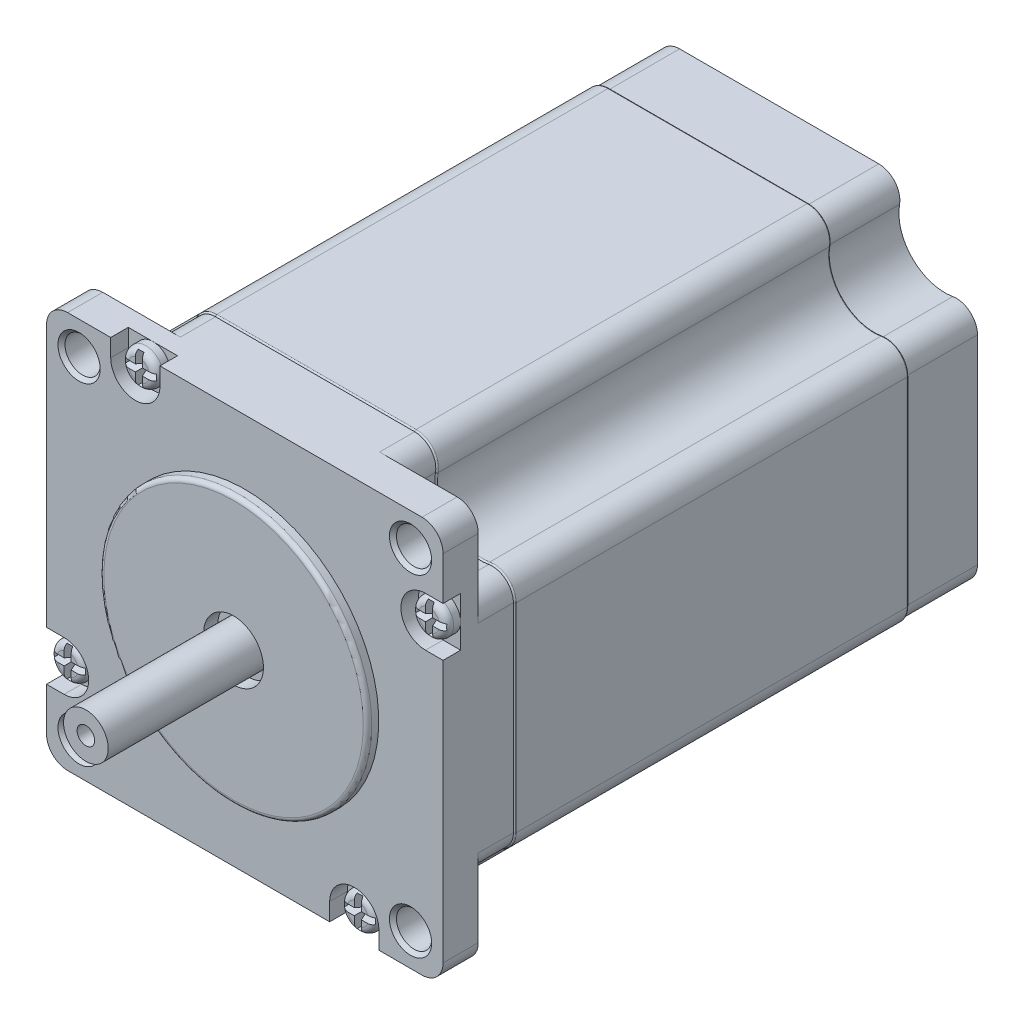
SolidWorks part; units mm, degrees
ref_plane "Front Plane" through (0, 0, 0) normal (0, 0, 1) x (1, 0, 0)
ref_plane "Top Plane" through (0, 0, 0) normal (0, 1, 0) x (1, 0, 0)
ref_plane "Right Plane" through (0, 0, 0) normal (1, 0, 0) x (0, 0, -1)
sketch "Sketch1" plane through (0, 0, 0) normal (0, 0, 1) x (1, 0, 0)
  line L1 (0, 0) -> (56.4, 0)
  line L2 (0, 0) -> (0, 56.4)
  line L3 (0, 56.4) -> (56.4, 56.4)
  line L4 (56.4, 0) -> (56.4, 56.4)
  dimension "D1" = 56.4
extrude "Boss-Extrude1" add sketch "Sketch1" along normal blind 76
sketch "Sketch2" plane through (0, 0, 76) normal (0, 0, 1) x (1, 0, 0)
  line L0 (28.2, 56.4) -> (28.2, 0) construction
  line L1 (56.4, 56.4) -> (0, 56.4) construction
  line L2 (0, 0) -> (56.4, 0) construction
  line L3 (28.2, 0) -> (0, 28.2) construction
  line L4 (0, 56.4) -> (0, 0) construction
  line L5 (0, 28.2) -> (56.4, 28.2) construction
  line L6 (56.4, 0) -> (56.4, 56.4) construction
  circle A0 centre (4.63, 51.77) radius 2.5
  circle A1 centre (51.77, 51.77) radius 2.5
  circle A2 centre (51.77, 4.63) radius 2.5
  circle A3 centre (4.63, 4.63) radius 2.5
  dimension "D3" = 5
  dimension "D1" = 23.57
  dimension "D2" = 47.14
extrude "Cut-Extrude1" cut sketch "Sketch2" against normal up to next
sketch "Sketch3" plane through (0, 0, 0) normal (0, 0, -1) x (-1, 0, 0)
  circle A0 centre (-51.77, 51.77) radius 6.5478
  circle A1 centre (-4.63, 51.77) radius 6.5478
  circle A2 centre (-4.63, 4.63) radius 6.5478
  circle A3 centre (-51.77, 4.63) radius 6.5478
extrude "Cut-Extrude2" cut sketch "Sketch3" against normal offset from surface (71 mm away) 5 up to face at (2.13, 4.63, 76)
fillet "Fillet1" radius 3 12 edges at (0, 9.26, 35.5) (9.26, 0, 35.5) (9.26, 56.4, 35.5) (0, 47.14, 35.5) (47.14, 0, 35.5) (56.4, 9.26, 35.5) (56.4, 47.14, 35.5) (47.14, 56.4, 35.5) (56.4, 56.4, 73.5) (56.4, 0, 73.5) (0, 56.4, 73.5) (0, 0, 73.5)
sketch "Sketch4" plane through (0, 0, 76) normal (0, 0, 1) x (1, 0, 0)
  line L0 (0, 28.2) -> (56.4, 28.2) construction
  line L1 (0, 53.4) -> (0, 3) construction
  line L2 (56.4, 3) -> (56.4, 53.4) construction
  circle A0 centre (28.2, 28.2) radius 19.05
  dimension "D1" = 38.1
extrude "Boss-Extrude2" add sketch "Sketch4" along normal blind 1.6
fillet "Fillet2" radius 0.6 1 edges at (47.25, 28.2, 77.6)
sketch "Sketch5" plane through (0, 0, 77.6) normal (0, 0, 1) x (1, 0, 0)
  line L0 (28.2, 46.65) -> (28.2, 28.2) construction
  circle A0 centre (28.2, 28.2) radius 18.45 construction
  circle A1 centre (28.2, 28.2) radius 3.175
  circle A2 centre (28.2, 28.2) radius 1.25
  dimension "D1" = 6.35
  dimension "D2" = 2.5
extrude "Boss-Extrude3" add sketch "Sketch5" along normal blind 21
sketch "Sketch6" plane through (0, 0, 77.6) normal (0, 0, 1) x (1, 0, 0)
  circle A0 centre (28.2, 28.2) radius 4.25
  circle A1 centre (28.2, 28.2) radius 3.175 construction
  circle A2 centre (28.2, 28.2) radius 3.175
  dimension "D1" = 8.5
extrude "Cut-Extrude3" cut sketch "Sketch6" against normal blind 2
ref_plane "Plane1" through (0, 0, 10) normal (0, 0, -1) x (-1, 0, 0)
sketch "Sketch7" plane through (0, 0, 10) normal (0, 0, -1) x (-1, 0, 0)
  line L0 (-56.4, 14.0376) -> (-56.4, 42.3624) construction
  line L1 (-42.3624, 56.4) -> (-14.0376, 56.4) construction
  line L2 (-56.4, 14.0376) -> (-56.4, 42.3624)
  line L3 (-42.3624, 56.4) -> (-14.0376, 56.4)
  line L4 (-56.2, 14.0376) -> (-56.2, 42.3624)
  line L5 (-42.3624, 56.2) -> (-14.0376, 56.2)
  line L6 (-42.3624, -0.2) -> (-14.0376, -0.2)
  line L7 (0.2, 14.0376) -> (0.2, 42.3624)
  line L8 (-42.3624, 0) -> (-14.0376, 0)
  line L9 (0, 14.0376) -> (0, 42.3624)
  line L10 (-14.0376, 56.4) -> (-42.3624, 56.4)
  line L11 (-56.4, 42.3624) -> (-56.4, 14.0376)
  line L12 (-42.3624, 0) -> (-14.0376, 0)
  line L13 (0, 14.0376) -> (0, 42.3624)
  line L14 (-14.0376, 56.4) -> (-42.3624, 56.4)
  line L15 (-56.4, 42.3624) -> (-56.4, 14.0376)
  line L16 (-14.0376, 56.6) -> (-42.3624, 56.6)
  line L17 (-56.6, 42.3624) -> (-56.6, 14.0376)
  arc A0 (-52.8878, 45.3183) -> (-56.4, 42.3624) centre (-53.4, 42.3624) ccw construction
  arc A1 (-52.8878, 45.3183) -> (-45.3183, 52.8878) centre (-51.77, 51.77) ccw construction
  arc A2 (-42.3624, 56.4) -> (-45.3183, 52.8878) centre (-42.3624, 53.4) ccw construction
  arc A3 (-52.8878, 45.3183) -> (-56.4, 42.3624) centre (-53.4, 42.3624) ccw
  arc A4 (-52.8878, 45.3183) -> (-45.3183, 52.8878) centre (-51.77, 51.77) ccw
  arc A5 (-42.3624, 56.4) -> (-45.3183, 52.8878) centre (-42.3624, 53.4) ccw
  arc A6 (-56.6, 14.0376) -> (-52.8537, 10.8846) centre (-53.4, 14.0376) ccw
  arc A7 (-45.5154, 3.5463) -> (-52.8537, 10.8846) centre (-51.77, 4.63) ccw
  arc A8 (-45.5154, 3.5463) -> (-42.3624, -0.2) centre (-42.3624, 3) ccw
  arc A9 (-14.0376, -0.2) -> (-10.8846, 3.5463) centre (-14.0376, 3) ccw
  arc A10 (-3.5463, 10.8846) -> (-10.8846, 3.5463) centre (-4.63, 4.63) ccw
  arc A11 (-3.5463, 10.8846) -> (0.2, 14.0376) centre (-3, 14.0376) ccw
  arc A12 (0.2, 42.3624) -> (-3.5463, 45.5154) centre (-3, 42.3624) ccw
  arc A13 (-10.8846, 52.8537) -> (-3.5463, 45.5154) centre (-4.63, 51.77) ccw
  arc A14 (-10.8846, 52.8537) -> (-14.0376, 56.6) centre (-14.0376, 53.4) ccw
  arc A15 (-52.8537, 45.5154) -> (-56.6, 42.3624) centre (-53.4, 42.3624) ccw
  arc A16 (-42.3624, 56.6) -> (-45.5154, 52.8537) centre (-42.3624, 53.4) ccw
  arc A17 (-42.3624, 56.6) -> (-45.5154, 52.8537) centre (-42.3624, 53.4) ccw
  arc A18 (-14.0376, 0) -> (-11.0817, 3.5122) centre (-14.0376, 3) ccw
  arc A19 (-3.5122, 11.0817) -> (-11.0817, 3.5122) centre (-4.63, 4.63) ccw
  arc A20 (-3.5122, 11.0817) -> (0, 14.0376) centre (-3, 14.0376) ccw
  arc A21 (0, 42.3624) -> (-3.5122, 45.3183) centre (-3, 42.3624) ccw
  arc A22 (-11.0817, 52.8878) -> (-3.5122, 45.3183) centre (-4.63, 51.77) ccw
  arc A23 (-11.0817, 52.8878) -> (-14.0376, 56.4) centre (-14.0376, 53.4) ccw
  arc A24 (-42.3624, 56.4) -> (-45.3183, 52.8878) centre (-42.3624, 53.4) ccw
  arc A25 (-52.8878, 45.3183) -> (-45.3183, 52.8878) centre (-51.77, 51.77) ccw
  arc A26 (-52.8878, 45.3183) -> (-56.4, 42.3624) centre (-53.4, 42.3624) ccw
  arc A27 (-56.4, 14.0376) -> (-52.8878, 11.0817) centre (-53.4, 14.0376) ccw
  arc A28 (-45.3183, 3.5122) -> (-52.8878, 11.0817) centre (-51.77, 4.63) ccw
  arc A29 (-45.3183, 3.5122) -> (-42.3624, 0) centre (-42.3624, 3) ccw
  arc A30 (-14.0376, 0) -> (-11.0817, 3.5122) centre (-14.0376, 3) ccw
  arc A31 (-3.5122, 11.0817) -> (-11.0817, 3.5122) centre (-4.63, 4.63) ccw
  arc A32 (-3.5122, 11.0817) -> (0, 14.0376) centre (-3, 14.0376) ccw
  arc A33 (0, 42.3624) -> (-3.5122, 45.3183) centre (-3, 42.3624) ccw
  arc A34 (-11.0817, 52.8878) -> (-3.5122, 45.3183) centre (-4.63, 51.77) ccw
  arc A35 (-11.0817, 52.8878) -> (-14.0376, 56.4) centre (-14.0376, 53.4) ccw
  arc A36 (-42.3624, 56.4) -> (-45.3183, 52.8878) centre (-42.3624, 53.4) ccw
  arc A37 (-52.8878, 45.3183) -> (-45.3183, 52.8878) centre (-51.77, 51.77) ccw
  arc A38 (-52.8878, 45.3183) -> (-56.4, 42.3624) centre (-53.4, 42.3624) ccw
  arc A39 (-56.4, 14.0376) -> (-52.8878, 11.0817) centre (-53.4, 14.0376) ccw
  arc A40 (-45.3183, 3.5122) -> (-52.8878, 11.0817) centre (-51.77, 4.63) ccw
  arc A41 (-45.3183, 3.5122) -> (-42.3624, 0) centre (-42.3624, 3) ccw
  arc A42 (-52.8537, 45.5154) -> (-45.5154, 52.8537) centre (-51.77, 51.77) ccw
  arc A43 (-52.8537, 45.5154) -> (-56.6, 42.3624) centre (-53.4, 42.3624) ccw
  dimension "D1" = 0
  dimension "D2" = 0.2
  dimension "D3" = 0.2
extrude "Boss-Extrude4" add sketch "Sketch7" against normal blind 56 contours A42 A15 L17 A6 A7 A8 L6 A9 A10 A11 L7 A12 A13 A14 L16 A16 A41 A40 A39 L2 A3 A4 A5 L3 A35 A34 A33 L13 A32 A31 A30 L12 region at (44.7492, 0.9912, 10)
fillet "Fillet4" radius 0.2 32 edges at (55.4606, 44.8106, 66) (56.6, 28.2, 66) (55.4606, 11.5894, 66) (47.2814, 9.1186, 66) (44.8106, 0.9394, 66) (28.2, -0.2, 66) (11.5894, 0.9394, 66) (9.1186, 9.1186, 66) (0.9394, 11.5894, 66) (-0.2, 28.2, 66) (0.9394, 44.8106, 66) (9.1186, 47.2814, 66) (11.5894, 55.4606, 66) (28.2, 56.6, 66) (44.8106, 55.4606, 66) (44.8106, 55.4606, 10) (28.2, 56.6, 10) (11.5894, 55.4606, 10) (9.1186, 47.2814, 10) (0.9394, 44.8106, 10) (-0.2, 28.2, 10) (0.9394, 11.5894, 10) (9.1186, 9.1186, 10) (11.5894, 0.9394, 10) (28.2, -0.2, 10) (44.8106, 0.9394, 10) (47.2814, 9.1186, 10) (55.4606, 11.5894, 10) (56.6, 28.2, 10) (47.2814, 47.2814, 66) (47.2814, 47.2814, 10) (55.4606, 44.8106, 10)
chamfer "Chamfer1" distance 0.5 angle 45 4 edges at (2.13, 4.63, 76) (54.27, 4.63, 76) (49.27, 51.77, 76) (7.13, 51.77, 76)
sketch "Sketch8" plane through (0, 0, 76) normal (0, 0, 1) x (1, 0, 0)
  line L0 (53.4, 56.4) -> (3, 56.4) construction
  line L1 (9.13, 53.9) -> (9.13, 56.4)
  line L2 (16.13, 53.9) -> (16.13, 56.4)
  line L3 (42.3624, 56.4) -> (14.0376, 56.4) construction
  line L4 (16.13, 56.4) -> (9.13, 56.4)
  arc A0 (9.13, 53.9) -> (16.13, 53.9) centre (12.63, 53.9) ccw
  circle A1 centre (12.63, 53.9) radius 2.5 construction
  circle A2 centre (4.63, 51.77) radius 2.5 construction
  dimension "D1" = 7
  dimension "D2" = 5
  dimension "D3" = 8
extrude "Cut-Extrude4" cut sketch "Sketch8" against normal blind 2.5
sketch "Sketch10" plane through (0, 0, 73.5) normal (0, 0, 1) x (1, 0, 0)
  circle A0 centre (12.63, 53.9) radius 2.5
extrude "Boss-Extrude5" add sketch "Sketch10" along normal blind 2
sketch "Sketch11" plane through (0, 0, 75.5) normal (0, 0, 1) x (1, 0, 0)
  line L0 (12.63, 56.4) -> (12.63, 51.4) construction
  line L1 (10.13, 53.9) -> (15.13, 53.9) construction
  line L2 (10.33, 53.4) -> (12.13, 53.4)
  line L3 (12.13, 56.2) -> (12.13, 54.4)
  line L4 (10.33, 54.4) -> (12.13, 54.4)
  line L5 (13.13, 56.2) -> (13.13, 54.4)
  line L6 (13.13, 53.4) -> (14.93, 53.4)
  line L7 (13.13, 54.4) -> (14.93, 54.4)
  line L8 (10.13, 53.4) -> (15.13, 53.4) construction
  line L9 (13.13, 53.4) -> (13.13, 51.6)
  line L10 (10.13, 54.4) -> (15.13, 54.4) construction
  line L11 (12.13, 53.4) -> (12.13, 51.6)
  line L12 (13.13, 56.4) -> (13.13, 51.4) construction
  line L13 (12.13, 56.2) -> (13.13, 56.2)
  line L14 (12.13, 56.4) -> (12.13, 51.4) construction
  line L15 (10.33, 54.4) -> (10.33, 53.4)
  line L17 (14.93, 54.4) -> (14.93, 53.4)
  line L18 (12.13, 51.6) -> (13.13, 51.6)
  line L21 (14.93, 56.4) -> (14.93, 51.4) construction
  line L24 (10.33, 56.4) -> (10.33, 51.4) construction
  circle A0 centre (12.63, 53.9) radius 2.5 construction
  point P26 (10.13, 51.6)
  point P30 (15.13, 51.6)
  point P33 (10.13, 56.2)
  point P34 (15.13, 56.2)
  dimension "D1" = 0.5
  dimension "D2" = 0.5
  dimension "D4" = 2.3
  dimension "D5" = 2.3
extrude "Cut-Extrude5" cut sketch "Sketch11" against normal blind 1.5 draft 16
fillet "Fillet5" radius 1 1 edges at (15.13, 53.9, 75.5)
pattern_circular "CirPattern3" count 4 over 360 about axis through (28.2, 28.2, 77.6) along (0, 0, 1) of "Cut-Extrude4"
pattern_circular "CirPattern4" count 4 over 360 about axis through (28.2, 28.2, 77.6) along (0, 0, 1) of "Fillet5", "Cut-Extrude5", "Boss-Extrude5"
